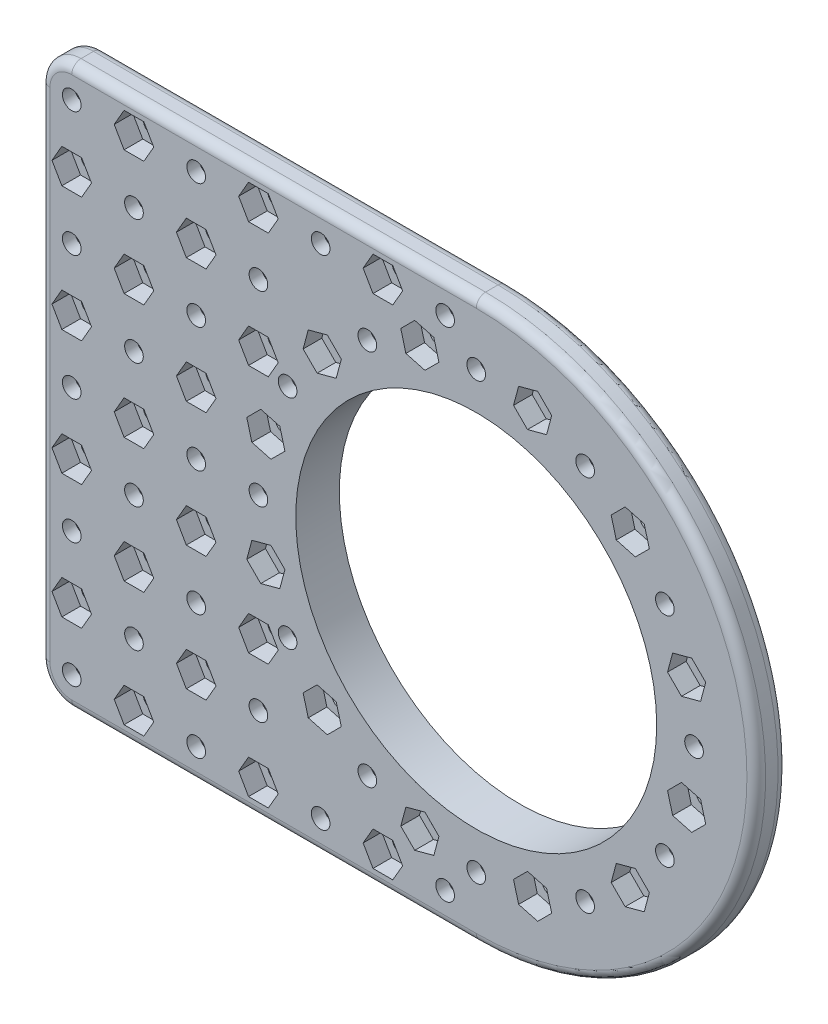
SolidWorks part; units mm, degrees
ref_plane "前视基准面" through (0, 0, 0) normal (0, 0, 1) x (1, 0, 0)
ref_plane "上视基准面" through (0, 0, 0) normal (0, 1, 0) x (1, 0, 0)
ref_plane "右视基准面" through (0, 0, 0) normal (1, 0, 0) x (0, 0, -1)
other "Configuration Table"
sketch "草图1" plane through (0, 0, 0) normal (0, 0, 1) x (1, 0, 0)
  line L1 (-35, -45) -> (35, -45)
  line L2 (-35, -45) -> (-35, 45)
  line L3 (-35, 45) -> (35, 45)
  line L4 (35, -45) -> (35, 45) construction
  line L5 (-35, -45) -> (35, 45) construction
  line L6 (-35, 45) -> (35, -45) construction
  arc A0 (35, -45) -> (35, 45) centre (35, 0) ccw
  point P0 (0, 0)
  dimension "D1" = 90
  dimension "D2" = 70
extrude "凸台-拉伸1" add sketch "草图1" along normal blind 5
sketch "草图2" plane through (0, 0, 5) normal (0, 0, 1) x (1, 0, 0)
  circle A0 centre (35, 0) radius 29
  dimension "D1" = 58
extrude "切除-拉伸1" cut sketch "草图2" against normal through all
sketch "草图3" plane through (0, 0, 0) normal (0, 0, 1) x (1, 0, 0)
  circle A0 centre (35, 0) radius 29
  circle A1 centre (35, 0) radius 45
  circle A2 centre (35, 0) radius 29 construction
  dimension "D1" = 90
extrude "凸台-拉伸2" add sketch "草图3" against normal blind 2
sketch "草图9" plane through (0, 0, -2) normal (0, 0, -1) x (-1, 0, 0)
  circle A0 centre (-35, 0) radius 45
  circle A1 centre (-35, 0) radius 31
  dimension "D1" = 62
extrude "切除-拉伸10" cut sketch "草图9" against normal blind 2
sketch "草图5" plane through (0, 0, 0) normal (0, 0, -1) x (-1, 0, 0)
  line L1 (-35, 35) -> (-35, 0) construction
  circle A0 centre (-35, 0) radius 35 construction
  circle A1 centre (-35, 35) radius 1.5
  dimension "D1" = 3
  dimension "D2" = 70
extrude "切除-拉伸2" cut sketch "草图5" against normal through all
sketch "草图6" plane through (0, 0, 0) normal (0, 0, -1) x (-1, 0, 0)
  line L0 (-35, 35) -> (-35, 0) construction
  line L1 (-35, 31.8246) -> (-32.25, 33.4123)
  line L2 (-32.25, 33.4123) -> (-32.25, 36.5877)
  line L3 (-32.25, 36.5877) -> (-35, 38.1754)
  line L4 (-35, 38.1754) -> (-37.75, 36.5877)
  line L5 (-37.75, 36.5877) -> (-37.75, 33.4123)
  line L6 (-37.75, 33.4123) -> (-35, 31.8246)
  circle A1 centre (-35, 35) radius 2.75 construction
  dimension "D1" = 5.5
extrude "切除-拉伸3" cut sketch "草图6" against normal blind 3
sketch "草图10" plane through (0, 0, -2) normal (0, 0, -1) x (-1, 0, 0)
  line L0 (-35, 0) -> (-25.9413, 33.8074) construction
  line L1 (-35, -1000) -> (-35, 49000) construction
  circle A0 centre (-25.9413, 33.8074) radius 1.5
  circle A1 centre (-35, 0) radius 35 construction
  dimension "D1" = 3
  dimension "D2" = 15
extrude "切除-拉伸11" cut sketch "草图10" against normal through all
sketch "草图11" plane through (0, 0, 5) normal (0, 0, 1) x (1, 0, 0)
  line L0 (25.9413, 33.8074) -> (35, 0) construction
  line L1 (26.7632, 30.7402) -> (29.0086, 32.9855)
  line L2 (29.0086, 32.9855) -> (28.1867, 36.0528)
  line L3 (28.1867, 36.0528) -> (25.1195, 36.8746)
  line L4 (25.1195, 36.8746) -> (22.8741, 34.6293)
  line L5 (22.8741, 34.6293) -> (23.696, 31.562)
  line L6 (23.696, 31.562) -> (26.7632, 30.7402)
  circle A0 centre (25.9413, 33.8074) radius 2.75 construction
  dimension "D1" = 5.5
extrude "切除-拉伸12" cut sketch "草图11" against normal blind 3
pattern_circular "阵列(圆周)1" count 12 over 360 about axis through (35, 0, 0) along (0, 0, 1) of "切除-拉伸3", "切除-拉伸2", "切除-拉伸11", "切除-拉伸12", "切除-拉伸1"
sketch "草图12" plane through (0, 0, 0) normal (0, 0, -1) x (-1, 0, 0)
  line L0 (35, 45) -> (35, -45) construction
  circle A0 centre (30, 0) radius 1.5
  dimension "D2" = 3
  dimension "D1" = 5
sketch "草图13" plane through (0, 0, 0) normal (0, 0, -1) x (-1, 0, 0)
  line L1 (26.8246, 0) -> (28.4123, -2.75)
  line L2 (28.4123, -2.75) -> (31.5877, -2.75)
  line L3 (31.5877, -2.75) -> (33.1754, 0)
  line L4 (33.1754, 0) -> (31.5877, 2.75)
  line L5 (31.5877, 2.75) -> (28.4123, 2.75)
  line L6 (28.4123, 2.75) -> (26.8246, 0)
  circle A1 centre (30, 0) radius 2.75 construction
  dimension "D1" = 5.5
extrude "切除-拉伸13" cut sketch "草图12" against normal through all
extrude "切除-拉伸14" cut sketch "草图13" against normal blind 3
pattern_linear "阵列(线性)1" count 5 spacing 10 along (0, -1, 0) count 5 spacing 10 along (0, 1, 0) of "切除-拉伸13"
pattern_linear "阵列(线性)2" count 3 spacing 10 along (1, 0, 0) of "阵列(线性)1", "切除-拉伸13"
pattern_linear "阵列(线性)3" count 3 spacing 20 along (0, -1, 0) count 3 spacing 20 along (0, 1, 0) of "切除-拉伸14"
sketch "草图15" plane through (0, 0, 5) normal (0, 0, 1) x (1, 0, 0)
  line L1 (-28.4123, 7.25) -> (-26.8246, 10)
  line L2 (-26.8246, 10) -> (-28.4123, 12.75)
  line L3 (-28.4123, 12.75) -> (-31.5877, 12.75)
  line L4 (-31.5877, 12.75) -> (-33.1754, 10)
  line L5 (-33.1754, 10) -> (-31.5877, 7.25)
  line L6 (-31.5877, 7.25) -> (-28.4123, 7.25)
  circle A0 centre (-30, 10) radius 2.75 construction
  dimension "D1" = 5.5
extrude "切除-拉伸16" cut sketch "草图15" against normal blind 3
pattern_linear "阵列(线性)5" count 3 spacing 20 along (0, -1, 0) count 3 spacing 20 along (0, 1, 0) of "切除-拉伸16"
pattern_linear "阵列(线性)4" count 2 spacing 20 along (1, 0, 0) of "阵列(线性)3", "阵列(线性)5", "切除-拉伸14", "切除-拉伸16"
sketch "草图14" plane through (0, 0, 0) normal (0, 0, -1) x (-1, 0, 0)
  line L0 (-1000, 0) -> (49000, 0) construction
  line L1 (0, -1000) -> (0, 49000) construction
  line L2 (-10, -1000) -> (-10, 49000) construction
  line L3 (-20, -1000) -> (-20, 49000) construction
  line L4 (-980, 40) -> (49020, 40) construction
  line L5 (-980, 30) -> (49020, 30) construction
  line L6 (-980, 20) -> (49020, 20) construction
  line L7 (-30, -960) -> (-30, 49040) construction
  circle A0 centre (0, 40) radius 1.5
  circle A1 centre (10, 0) radius 1.5 construction
  circle A2 centre (0, 30) radius 1.5
  circle A3 centre (-10, 40) radius 1.5
  circle A4 centre (-20, 40) radius 1.5
  circle A6 centre (0, 20) radius 1.5
  circle A9 centre (-30, 40) radius 1.5
  dimension "D1" = 10
  dimension "D2" = 3
  dimension "D3" = 10
  dimension "D4" = 10
  dimension "D5" = 10
extrude "切除-拉伸15" cut sketch "草图14" against normal through all
sketch "草图16" plane through (0, 0, 0) normal (0, 0, -1) x (-1, 0, 0)
  line L1 (23.1754, 30) -> (21.5877, 32.75)
  line L2 (21.5877, 32.75) -> (18.4123, 32.75)
  line L3 (18.4123, 32.75) -> (16.8246, 30)
  line L4 (16.8246, 30) -> (18.4123, 27.25)
  line L5 (18.4123, 27.25) -> (21.5877, 27.25)
  line L6 (21.5877, 27.25) -> (23.1754, 30)
  line L7 (23.1754, 10) -> (21.5877, 12.75)
  line L8 (21.5877, 12.75) -> (18.4123, 12.75)
  line L9 (18.4123, 12.75) -> (16.8246, 10)
  line L10 (16.8246, 10) -> (18.4123, 7.25)
  line L11 (18.4123, 7.25) -> (21.5877, 7.25)
  line L12 (21.5877, 7.25) -> (23.1754, 10)
  line L13 (3.1754, 30) -> (1.5877, 32.75)
  line L14 (1.5877, 32.75) -> (-1.5877, 32.75)
  line L15 (-1.5877, 32.75) -> (-3.1754, 30)
  line L16 (-3.1754, 30) -> (-1.5877, 27.25)
  line L17 (-1.5877, 27.25) -> (1.5877, 27.25)
  line L18 (1.5877, 27.25) -> (3.1754, 30)
  line L19 (-6.8246, 40) -> (-8.4123, 42.75)
  line L20 (-8.4123, 42.75) -> (-11.5877, 42.75)
  line L21 (-11.5877, 42.75) -> (-13.1754, 40)
  line L22 (-13.1754, 40) -> (-11.5877, 37.25)
  line L23 (-11.5877, 37.25) -> (-8.4123, 37.25)
  line L24 (-8.4123, 37.25) -> (-6.8246, 40)
  line L25 (-26.8246, 40) -> (-28.4123, 42.75)
  line L26 (-28.4123, 42.75) -> (-31.5877, 42.75)
  line L27 (-31.5877, 42.75) -> (-33.1754, 40)
  line L28 (-33.1754, 40) -> (-31.5877, 37.25)
  line L29 (-31.5877, 37.25) -> (-28.4123, 37.25)
  line L30 (-28.4123, 37.25) -> (-26.8246, 40)
  circle A0 centre (20, 30) radius 2.75 construction
  circle A1 centre (20, 10) radius 2.75 construction
  circle A2 centre (0, 30) radius 2.75 construction
  circle A3 centre (-10, 40) radius 2.75 construction
  circle A4 centre (-30, 40) radius 2.75 construction
  dimension "D1" = 5.5
extrude "切除-拉伸17" cut sketch "草图16" against normal blind 3
sketch "草图17" plane through (0, 0, 5) normal (0, 0, 1) x (1, 0, 0)
  line L1 (-16.8246, 40) -> (-18.4123, 42.75)
  line L2 (-18.4123, 42.75) -> (-21.5877, 42.75)
  line L3 (-21.5877, 42.75) -> (-23.1754, 40)
  line L4 (-23.1754, 40) -> (-21.5877, 37.25)
  line L5 (-21.5877, 37.25) -> (-18.4123, 37.25)
  line L6 (-18.4123, 37.25) -> (-16.8246, 40)
  line L7 (3.1754, 40) -> (1.5877, 42.75)
  line L8 (1.5877, 42.75) -> (-1.5877, 42.75)
  line L9 (-1.5877, 42.75) -> (-3.1754, 40)
  line L10 (-3.1754, 40) -> (-1.5877, 37.25)
  line L11 (-1.5877, 37.25) -> (1.5877, 37.25)
  line L12 (1.5877, 37.25) -> (3.1754, 40)
  line L13 (23.1754, 40) -> (21.5877, 42.75)
  line L14 (21.5877, 42.75) -> (18.4123, 42.75)
  line L15 (18.4123, 42.75) -> (16.8246, 40)
  line L16 (16.8246, 40) -> (18.4123, 37.25)
  line L17 (18.4123, 37.25) -> (21.5877, 37.25)
  line L18 (21.5877, 37.25) -> (23.1754, 40)
  line L19 (-16.8246, 20) -> (-18.4123, 22.75)
  line L20 (-18.4123, 22.75) -> (-21.5877, 22.75)
  line L21 (-21.5877, 22.75) -> (-23.1754, 20)
  line L22 (-23.1754, 20) -> (-21.5877, 17.25)
  line L23 (-21.5877, 17.25) -> (-18.4123, 17.25)
  line L24 (-18.4123, 17.25) -> (-16.8246, 20)
  line L25 (-16.8246, 0) -> (-18.4123, 2.75)
  line L26 (-18.4123, 2.75) -> (-21.5877, 2.75)
  line L27 (-21.5877, 2.75) -> (-23.1754, 0)
  line L28 (-23.1754, 0) -> (-21.5877, -2.75)
  line L29 (-21.5877, -2.75) -> (-18.4123, -2.75)
  line L30 (-18.4123, -2.75) -> (-16.8246, 0)
  line L31 (3.1754, 20) -> (1.5877, 22.75)
  line L32 (1.5877, 22.75) -> (-1.5877, 22.75)
  line L33 (-1.5877, 22.75) -> (-3.1754, 20)
  line L34 (-3.1754, 20) -> (-1.5877, 17.25)
  line L35 (-1.5877, 17.25) -> (1.5877, 17.25)
  line L36 (1.5877, 17.25) -> (3.1754, 20)
  circle A0 centre (-20, 40) radius 2.75 construction
  circle A1 centre (0, 40) radius 2.75 construction
  circle A2 centre (20, 40) radius 2.75 construction
  circle A3 centre (-20, 20) radius 2.75 construction
  circle A4 centre (-20, 0) radius 2.75 construction
  circle A5 centre (0, 20) radius 2.75 construction
  point P46 (0, 0)
  dimension "D1" = 5.5
extrude "切除-拉伸18" cut sketch "草图17" against normal blind 3
mirror "镜向1" about plane through (0, 0, 0) normal (0, 1, 0) of "切除-拉伸15", "切除-拉伸17", "切除-拉伸18"
fillet "圆角4" radius 1.5 8 edges at (0, -45, 5) (0, -45, 0) (80, 0, 0) (0, 45, 5) (0, 45, 0) (80, 0, 5) (-35, 0, 5) (-35, 0, 0)
fillet "圆角5" radius 5 6 edges at (-34.5607, -44.5607, 0.4393) (-34.5607, -44.5607, 4.5607) (-34.5607, 44.5607, 0.4393) (-34.5607, 44.5607, 4.5607) (-35, 45, 2.5) (-35, -45, 2.5)
